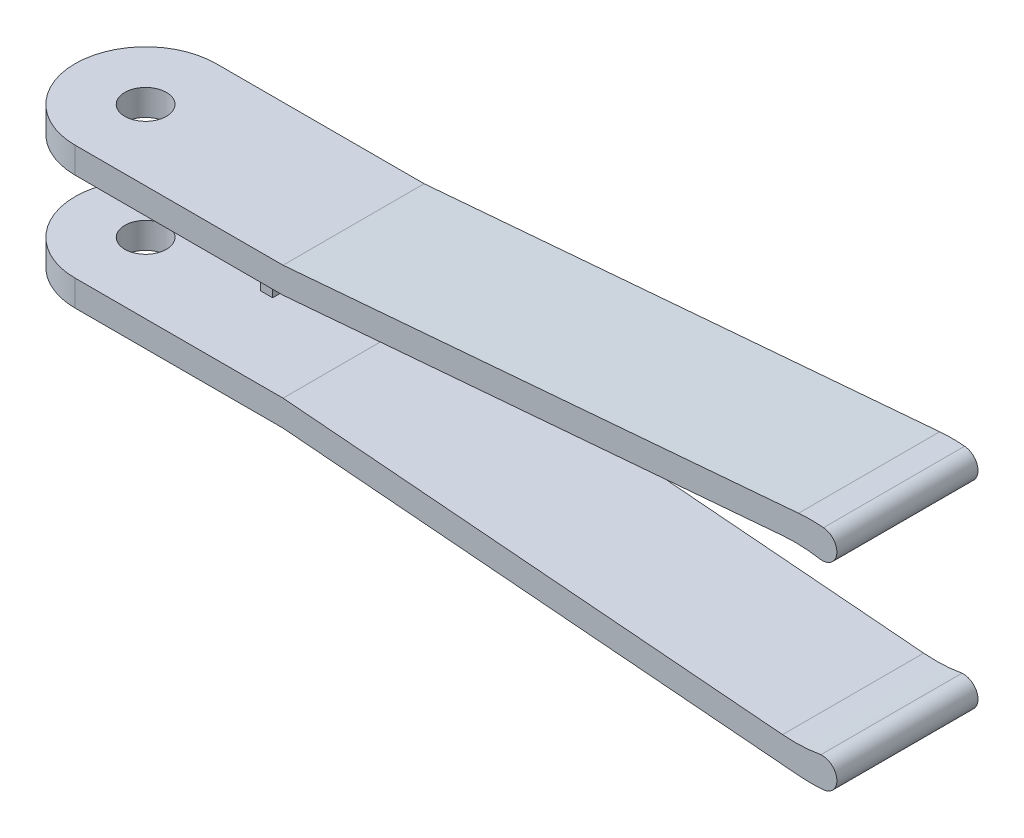
SolidWorks part; units mm, degrees
ref_plane "前视基准面" through (0, 0, 0) normal (0, 0, 1) x (1, 0, 0)
ref_plane "上视基准面" through (0, 0, 0) normal (0, 1, 0) x (1, 0, 0)
ref_plane "右视基准面" through (0, 0, 0) normal (1, 0, 0) x (0, 0, -1)
other "Configuration Table"
sketch "草图1" plane through (0, 0, 0) normal (0, 1, 0) x (1, 0, 0)
  circle A0 centre (0, 0) radius 1.4
  circle A1 centre (0, 0) radius 4.75
  dimension "D1" = 2.8
  dimension "D2" = 9.5
extrude "凸台-拉伸1" add sketch "草图1" along normal blind 1.75
sketch "草图2" plane through (0, 0, 0) normal (0, 0, 1) x (1, 0, 0)
  line L0 (14, 1.75) -> (50, 4.75)
  line L2 (14, 0) -> (48.9217, 2.9101)
  line L3 (50, 4.75) -> (70, 1.2)
  line L4 (65.3168, 0) -> (70, 0)
  line L5 (48.9217, 2.9101) -> (65.3168, 0)
  line L6 (70, 1.2) -> (70, 0)
  line L7 (4.75, 1.75) -> (-4.75, 1.75) construction
  line L8 (-4.75, 0) -> (4.75, 0) construction
  line L9 (14, 0) -> (0, 0)
  line L10 (0, 0) -> (0, 1.75)
  line L11 (1.4, 1.75) -> (-1.4, 1.75) construction
  line L12 (0, 1.75) -> (14, 1.75)
  line L13 (14, 0) -> (14, 1.75) construction
  dimension "D1" = 3
  dimension "D2" = 70
  dimension "D3" = 20
  dimension "D4" = 2
  dimension "D5" = 1.2
  dimension "DIM0" = 14
extrude "凸台-拉伸2" add sketch "草图2" along normal blind 4.75 and the other way blind 4.75
sketch "草图3" plane through (0, 1.75, 0) normal (0, 1, 0) x (1, 0, 0)
  circle A0 centre (0, 0) radius 1.4
extrude "切除-拉伸1" cut sketch "草图3" against normal through all
fillet "圆角1" radius 10 2 edges at (50, 4.75, 0) (48.9217, 2.9101, 0)
fillet "圆角2" radius 10 1 edges at (65.3168, 0, 0)
sketch "草图4" plane through (0, 0, 4.75) normal (0, 0, 1) x (1, 0, 0)
  line L0 (14, 1.75) -> (14, 0) construction
  line L1 (16, 0.1667) -> (20.9827, 0.5819) construction
  line L2 (14, 0) -> (47.6248, 2.8021) construction
  line L3 (15.9917, 0.2663) -> (20.9744, 0.6815)
  line L4 (16.0083, 0.067) -> (20.991, 0.4822)
  arc A2 (15.9917, 0.2663) -> (16.0083, 0.067) centre (16, 0.1667) ccw
  arc A3 (20.991, 0.4822) -> (20.9744, 0.6815) centre (20.9827, 0.5819) ccw
  point P4 (18.4914, 0.3743)
  dimension "D1" = 2
  dimension "DIM1" = 0.1
  dimension "DIM2" = 5
sketch "草图5" plane through (0, 0, 4.75) normal (0, 0, 1) x (1, 0, 0)
  line L1 (70, 0) -> (51.2813, 0)
  line L2 (70, 0) -> (70, 4.5226)
  line L3 (70, 4.5226) -> (51.2813, 4.5226)
  line L4 (51.2813, 0) -> (51.2813, 4.5226)
extrude "切除-拉伸3" cut sketch "草图5" against normal through all
sketch "草图6" plane through (0, 0, 4.75) normal (0, 0, 1) x (1, 0, 0)
  line L0 (51.2813, 4.5226) -> (51.2813, 2.4913) construction
  line L3 (51.2813, 4.5226) -> (51.2813, 3.6623)
  arc A0 (51.2813, 3.6623) -> (50.3831, 4.6403) centre (50.2997, 3.6623) ccw
  arc A1 (51.2813, 4.5226) -> (48.7032, 4.6419) centre (49.5336, -5.3235) ccw construction
  arc A2 (50.203, 2.6827) -> (47.6248, 2.8021) centre (48.4553, -7.1634) ccw construction
  arc A3 (51.2813, 4.5226) -> (50.3831, 4.6403) centre (49.5336, -5.3235) ccw
extrude "切除-拉伸4" cut sketch "草图6" against normal through all
sketch "草图7" plane through (0, 0, 4.75) normal (0, 0, 1) x (1, 0, 0)
  line L0 (51.2813, 3.6623) -> (51.2813, 2.4913) construction
  line L1 (50.203, 2.6827) -> (51.2813, 2.4913) construction
  line L2 (51.2813, 3.6623) -> (51.2813, 2.4913)
  line L3 (50.1505, 2.692) -> (51.2813, 2.4913)
  arc A0 (50.1505, 2.692) -> (51.2813, 3.6623) centre (50.2997, 3.6623) ccw
  arc A1 (51.2813, 3.6623) -> (50.3831, 4.6403) centre (50.2997, 3.6623) ccw construction
  line M2 (51.2813, 2.4913) -> (51.2813, 3.6623)
  line M15 (50.203, 2.6827) -> (51.2813, 2.4913)
extrude "切除-拉伸5" cut sketch "草图7" against normal through all contours A0 L3 M15 M2 region at (51.0168, 2.8072, 4.75)
sketch "草图10" plane through (0, 0, 0) normal (0, -1, 0) x (1, 0, 0)
  line L0 (0, -4.75) -> (14, -4.75) construction
  line L1 (7.8, -0.75) -> (7, -0.75)
  line L2 (7.8, -0.75) -> (7.8, -4.75)
  line L3 (7.8, -4.75) -> (7, -4.75)
  line L4 (7, -0.75) -> (7, -4.75)
  point P7 (7, 4.75)
  point P9 (7.8, 4.75)
  dimension "D1" = 0.8
  dimension "D2" = 7
  dimension "D3" = 4
extrude "凸台-拉伸3" add sketch "草图10" along normal blind 3
mirror "镜向1" about plane through (0, -3, 0) normal (0, 1, 0) of bodies 117
